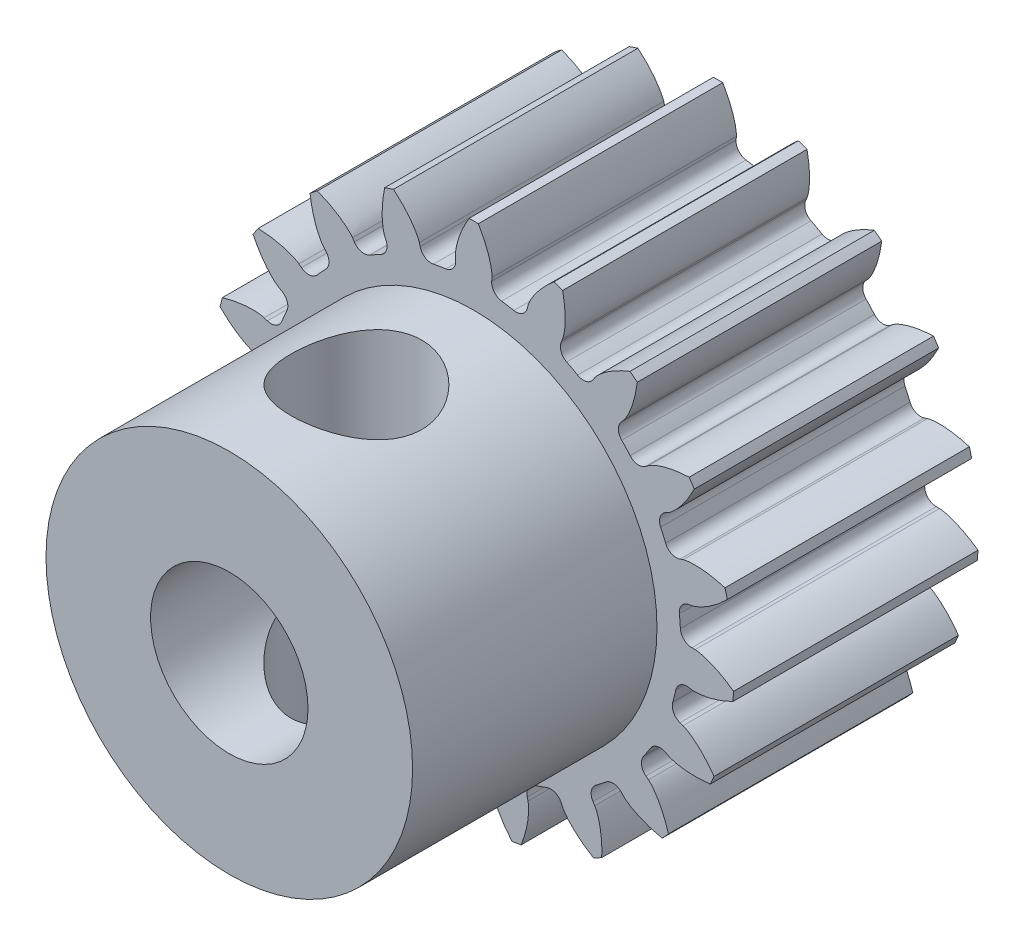
SolidWorks part; units mm, degrees
note: '?' marks a value the reader was unsure of.
ref_plane "Front Plane" through (0, 0, 0) normal (0, 0, 1) x (1, 0, 0)
ref_plane "Top Plane" through (0, 0, 0) normal (0, 1, 0) x (1, 0, 0)
ref_plane "Right Plane" through (0, 0, 0) normal (1, 0, 0) x (0, 0, -1)
sketch "Sketch1" plane through (0, 0, 0) normal (1, 0, 0) x (0, 0, -1)
  line L1 (-6.35, 6.7681) -> (0, 6.7681)
  line L2 (-6.35, 6.7681) -> (-6.35, 0)
  line L3 (-6.35, 0) -> (0, 0)
  line L4 (0, 6.7681) -> (0, 0)
  dimension "D1" = 6.7681
  dimension "D2" = 6.35
revolve "Revolve1" add sketch "Sketch1" angle 360 about L3
sketch "Sketch2" plane through (0, 0, 6.35) normal (0, 0, 1) x (1, 0, 0)
  circle A0 centre (0, 0) radius 2.045
  dimension "D1" = 4.09
extrude "Cut-Extrude1" cut sketch "Sketch2" against normal up to surface (6.35 mm away) up to face at (6.7681, 0, 0)
sketch "Sketch3" plane through (0, 0, 6.35) normal (0, 0, 1) x (1, 0, 0)
  line L0 (0, 0) -> (-5.7542, 0) construction
  line L1 (0, 0) -> (-5.747, -0.2876) construction
  line L2 (0, 0) -> (-5.7254, -0.5745) construction
  line L3 (0, 0) -> (-5.6896, -0.8599) construction
  line L4 (0, 0) -> (-5.6395, -1.1432) construction
  line L5 (0, 0) -> (-5.5753, -1.4236) construction
  line L6 (0, 0) -> (-5.4972, -1.7005) construction
  line L7 (0, 0) -> (-5.4053, -1.9731) construction
  line L8 (0, 0) -> (-5.3, -2.2408) construction
  line L9 (0, 0) -> (-5.1813, -2.5029) construction
  line L10 (0, 0) -> (-5.0498, -2.7587) construction
  line L11 (0, 0) -> (-4.9056, -3.0076) construction
  line L12 (0, 0) -> (-4.7491, -3.2491) construction
  line L13 (0, 0) -> (-4.5808, -3.4824) construction
  line L14 (-5.747, -0.2876) -> (-5.9339, 3.448) construction
  line L15 (-5.7254, -0.5745) -> (-6.0988, 3.1471) construction
  line L16 (-5.6896, -0.8599) -> (-6.2485, 2.8383) construction
  line L17 (-5.6395, -1.1432) -> (-6.3826, 2.5225) construction
  line L18 (-5.5753, -1.4236) -> (-6.5007, 2.2003) construction
  line L19 (-5.4972, -1.7005) -> (-6.6025, 1.8727) construction
  line L20 (-5.4053, -1.9731) -> (-6.6878, 1.5404) construction
  line L21 (-5.3, -2.2408) -> (-6.7565, 1.2042) construction
  line L22 (-5.1813, -2.5029) -> (-6.8082, 0.865) construction
  line L23 (-5.0498, -2.7587) -> (-6.8429, 0.5236) construction
  line L24 (-4.9056, -3.0076) -> (-6.8606, 0.181) construction
  line L25 (-4.7491, -3.2491) -> (-6.861, -0.1621) construction
  line L26 (-4.5808, -3.4824) -> (-6.8444, -0.5048) construction
  line L27 (0, 0) -> (-4.4011, -3.707) construction
  line L28 (-4.4011, -3.707) -> (-6.9959, -0.6262) construction
  line L29 (0, 0) -> (-6.7449, 0.5589) construction
  line L30 (-5.7542, 0) -> (-5.6686, 0)
  line L31 (-5.6757, 0.9471) -> (-5.5913, 0.933)
  circle A0 centre (0, 0) radius 6.1235 construction
  circle A1 centre (0, 0) radius 5.3777 construction
  circle A2 centre (0, 0) radius 6.7681 construction
  circle A3 centre (0, 0) radius 5.7542 construction
  arc A4 (-5.3703, 0.283) -> (-5.3436, 0.6047) centre (0, 0) cw
  arc A5 (-5.6686, 0) -> (-5.3703, 0.283) centre (-5.6686, 0.2988) ccw
  arc A6 (-5.3436, 0.6047) -> (-5.5913, 0.933) centre (-5.6405, 0.6383) ccw
  spline S0 degree 3 poles (-5.7542, 0) (-5.7638, -0.0002) (-5.7853, -0.0019) (-5.8234, -0.0068) (-5.8729, -0.0158) (-5.936, -0.0304) (-6.0121, -0.0521) (-6.1007, -0.0821) (-6.2011, -0.1218) (-6.3124, -0.1724) (-6.4339, -0.2351) (-6.5646, -0.311) (-6.7577, -0.4364) (-6.9006, -0.5459) (-6.9959, -0.6262) knots 0 0 0 0 0.020408 0.045919 0.081633 0.127551 0.183674 0.25 0.326531 0.413266 0.510204 0.617347 0.734694 1 1 1 1
  spline S1 degree 3 poles (-5.6757, 0.9471) (-5.6851, 0.9489) (-5.7061, 0.9541) (-5.7428, 0.9652) (-5.7902, 0.9822) (-5.85, 1.007) (-5.9216, 1.0409) (-6.004, 1.0851) (-6.0964, 1.1408) (-6.198, 1.209) (-6.3075, 1.2909) (-6.4239, 1.3872) (-6.5937, 1.5427) (-6.7166, 1.6743) (-6.7974, 1.7692) knots 0 0 0 0 0.020408 0.045919 0.081633 0.127551 0.183674 0.25 0.326531 0.413266 0.510204 0.617347 0.734694 1 1 1 1
  point P8 (-6.6986, -0.3996)
  point P10 (-6.5598, -0.3096)
  point P54 (-6.4291, -0.2338)
  point P56 (-6.3076, -0.1713)
  point P57 (-6.1963, -0.1208)
  point P58 (-6.0959, -0.0812)
  point P59 (-6.0073, -0.0513)
  point P60 (-5.9312, -0.0298)
  point P61 (-5.8681, -0.0153)
  point P62 (-5.8186, -0.0065)
  point P63 (-5.7829, -0.0019)
  point P64 (-5.7614, -0.0002)
  point P101 (-5.3777, 0)
  point P104 (-5.3044, 0.8851)
  point P105 (-6.1228, -0.0913)
  point P106 (-6.0243, 1.0978)
  dimension "D1" = 10.7554
  dimension "Standard Pitch Diameter" = 12.247
  dimension "D2" = 11.5084
  dimension "D3" = 14
  dimension "D25" = 0.2988
  dimension "D4" = 2.865
  dimension "D5" = 13
  dimension "D6" = 90
  dimension "D7" = 3.7402
  dimension "D8" = 3.4525
  dimension "D9" = 3.1648
  dimension "D10" = 2.8771
  dimension "D11" = 2.5894
  dimension "D12" = 2.3017
  dimension "D13" = 2.014
  dimension "D14" = 1.7263
  dimension "D15" = 1.4385
  dimension "D16" = 0.2877
  dimension "D17" = 0.5754
  dimension "D18" = 0.8631
  dimension "D19" = 1.1508
  dimension "D20" = 2.865
  dimension "D21" = 90
  dimension "D22" = 4.0279
  dimension "D23" = 4.737
  dimension "D26" = 1.195
extrude "Cut-Extrude2" cut sketch "Sketch3" against normal through all and the other way through all
pattern_circular "CirPattern1" count 19 over 360 about axis through (0, 0, 0) along (0, 0, 1) of "Cut-Extrude2"
ref_axis "Axis1" through (0, 0, -0.844) along (0, 0, 1)?
sketch "Sketch4" plane through (0, 0, 6.35) normal (0, 0, 1) x (1, 0, 0)
  circle A0 centre (0, 0) radius 2.045
  circle A1 centre (0, 0) radius 4.7625
  circle A2 centre (0, 0) radius 2.045 construction
  dimension "D1" = 9.525
extrude "Boss-Extrude1" add sketch "Sketch4" along normal blind 6.35
sketch "Sketch5" plane through (0, 0, 0) normal (0, 1, 0) x (1, 0, 0)
  line L0 (0, 0.844) -> (0, -17.724) construction
  line L1 (-4.7625, -12.7) -> (4.7625, -12.7) construction
  circle A0 centre (0, -9.398) radius 1.7
  point P0 (0, -9.398)
  dimension "D2" = 3.4
  dimension "D1" = 3.302
extrude "Cut-Extrude3" cut sketch "Sketch5" against normal up to surface and the other way up to surface up to face at (4.7625, 0, 12.7) other way up to face at (4.7625, 0, 12.7)
equation "\"Width\"= 6.35"
equation "\"Circular Pitch\"= 2.025"
equation "\"Pressure Angle\"= 20"
equation "\"Number of Teeth\"= 19"
equation "\"Standard Pitch Diameter@Sketch3\" = \"Number of Teeth\" * \"Circular Pitch\"/Pi"
equation "\"D1@Sketch1\" =(2* \"Circular Pitch\"/Pi + \"Standard Pitch Diameter@Sketch3\")/2"
equation "\"D2@Sketch1\" = \"Width\""
equation "\"Shaft Diameter\"= 4.09"
equation "\"D1@Sketch2\" = \"Shaft Diameter\""
equation "\"D2@Sketch3\" = \"Standard Pitch Diameter@Sketch3\" *  cos( \"Pressure Angle\" ) "
equation "\"D1@Sketch3\" =\"Standard Pitch Diameter@Sketch3\"-2*1.157* \"Circular Pitch\"/Pi"
equation "\"D7@Sketch3\" = \"D2@Sketch3\"/40*13"
equation "\"D8@Sketch3\" = \"D2@Sketch3\"/40*12"
equation "\"D9@Sketch3\" = \"D2@Sketch3\"/40*11"
equation "\"D10@Sketch3\" = \"D2@Sketch3\"/40*10"
equation "\"D11@Sketch3\" = \"D2@Sketch3\"/40*9"
equation "\"D12@Sketch3\" = \"D2@Sketch3\"/40*8"
equation "\"D13@Sketch3\" = \"D2@Sketch3\"/40*7"
equation "\"D14@Sketch3\" = \"D2@Sketch3\"/40*6"
equation "\"D15@Sketch3\" = \"D2@Sketch3\"/40*5"
equation "\"D16@Sketch3\" = \"D2@Sketch3\"/40*1"
equation "\"D17@Sketch3\" = \"D2@Sketch3\"/40*2"
equation "\"D18@Sketch3\" = \"D2@Sketch3\"/40*3"
equation "\"D19@Sketch3\" = \"D2@Sketch3\"/40*4"
equation "\"D22@Sketch3\" = \"D2@Sketch3\"/40*14"
equation "\"D4@Sketch3\" = 360/((\"D2@Sketch3\"*Pi)/(\"D2@Sketch3\"/40))"
equation "\"D20@Sketch3\" = \"D4@Sketch3\""
equation "\"D23@Sketch3\" = (360/\"Number of Teeth\")/4"
equation "\"D2@CirPattern1\" = 360/\"Number of Teeth\""
equation "\"D1@CirPattern1\"=\"Number of Teeth\""
equation "\"D25@Sketch3\" = \"D26@Sketch3\"/4"
